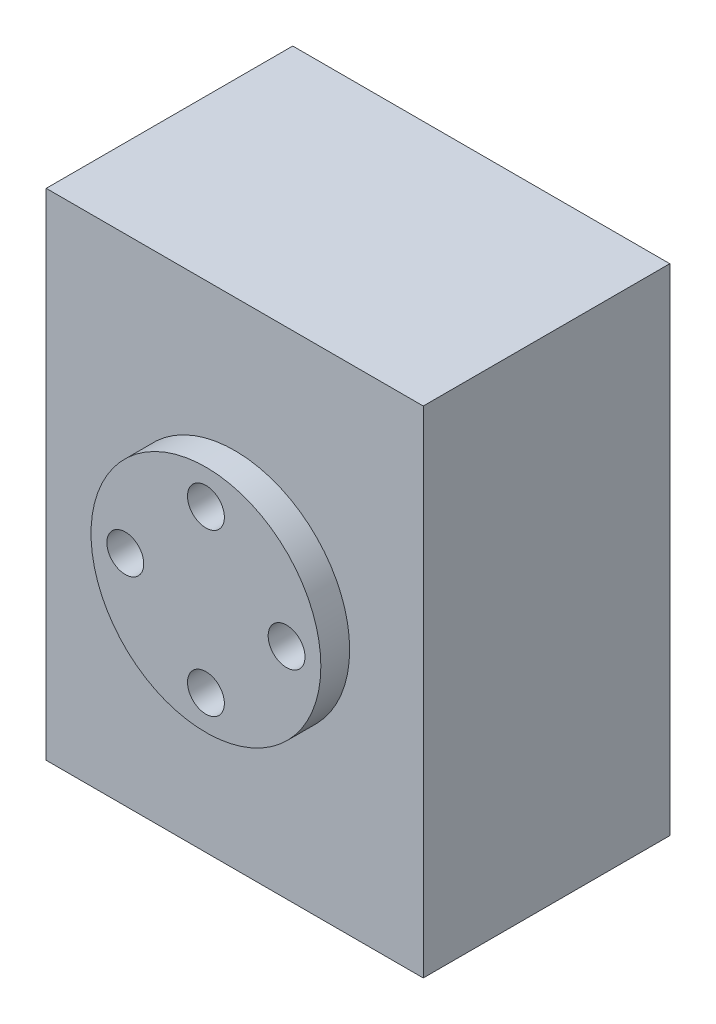
SolidWorks part; units mm, degrees
ref_plane "Front Plane" through (0, 0, 0) normal (0, 0, 1) x (1, 0, 0)
ref_plane "Top Plane" through (0, 0, 0) normal (0, 1, 0) x (1, 0, 0)
ref_plane "Right Plane" through (0, 0, 0) normal (1, 0, 0) x (0, 0, -1)
sketch "Sketch1" plane through (0, 0, 0) normal (0, 0, 1) x (1, 0, 0)
  circle A0 centre (0, 0) radius 9.975
  dimension "D1" = 19.95
extrude "Boss-Extrude1" add sketch "Sketch1" along normal blind 2.5
sketch "Sketch3" plane through (0, 0, 0) normal (0, 0, -1) x (-1, 0, 0)
  line L0 (16.365, 21.5) -> (16.365, -21.5)
  line L1 (-12.365, 17.5) -> (12.365, 17.5)
  line L2 (-12.365, 17.5) -> (-12.365, -17.5)
  line L3 (-12.365, -17.5) -> (12.365, -17.5)
  line L4 (12.365, 17.5) -> (12.365, -17.5)
  line L5 (-12.365, 17.5) -> (12.365, -17.5) construction
  line L6 (-12.365, -17.5) -> (12.365, 17.5) construction
  line L7 (-16.365, -21.5) -> (16.365, -21.5)
  line L8 (-16.365, 21.5) -> (-16.365, -21.5)
  line L9 (-16.365, 21.5) -> (16.365, 21.5)
  point P0 (0, 0)
  dimension "D1" = 35
  dimension "D2" = 24.73
  dimension "D3" = 4
extrude "Boss-Extrude4" add sketch "Sketch3" along normal blind 2.5 contours L2 L1 L4 L3
extrude "Boss-Extrude5" add sketch "Sketch3<5>" along normal blind 21.4
sketch "Sketch3<5>" plane through (0, 0, 0) normal (0, 0, -1) x (-1, 0, 0) same geometry as "Sketch3"
sketch "Sketch4" plane through (0, 0, -2.5) normal (0, 0, -1) x (-1, 0, 0)
  line L1 (12.365, 17.5) -> (7.165, 17.5)
  line L2 (12.365, 17.5) -> (12.365, 16.4)
  line L3 (12.365, 16.4) -> (7.165, 16.4)
  line L4 (7.165, 17.5) -> (7.165, 16.4)
  line L5 (-12.365, 17.5) -> (-7.165, 17.5)
  line L6 (-12.365, 17.5) -> (-12.365, 16.4)
  line L7 (-12.365, 16.4) -> (-7.165, 16.4)
  line L8 (-7.165, 17.5) -> (-7.165, 16.4)
  line L9 (12.365, -17.5) -> (9.165, -17.5)
  line L10 (12.365, -17.5) -> (12.365, -16)
  line L11 (12.365, -16) -> (9.165, -16)
  line L12 (9.165, -17.5) -> (9.165, -16)
  line L13 (-12.365, -17.5) -> (-9.165, -17.5)
  line L14 (-12.365, -17.5) -> (-12.365, -16)
  line L15 (-12.365, -16) -> (-9.165, -16)
  line L16 (-9.165, -17.5) -> (-9.165, -16)
  dimension "D1" = 1.1
  dimension "D2" = 5.2
  dimension "D3" = 5.2
  dimension "D4" = 1.1
  dimension "D5" = 3.2
  dimension "D6" = 1.5
  dimension "D7" = 3.2
extrude "Boss-Extrude6" add sketch "Sketch4" along normal blind 18.9 contours L2 L1 L4 L3 | L6 L5 L8 L7 | L10 L9 L12 L11 | L14 L13 L16 L15
sketch "Sketch6" plane through (0, 0, -2.5) normal (0, 0, -1) x (-1, 0, 0)
  line L1 (9.165, -17.5) -> (-9.165, -17.5)
  line L2 (9.165, -17.5) -> (9.165, -16)
  line L3 (9.165, -16) -> (-9.165, -16)
  line L4 (-9.165, -17.5) -> (-9.165, -16)
extrude "Boss-Extrude7" add sketch "Sketch6" along normal blind 5.3
sketch "Sketch2" plane through (0, 0, 2.5) normal (0, 0, 1) x (1, 0, 0)
  circle A0 centre (0, 0) radius 7 construction
  circle A1 centre (7, 0) radius 1.6
  circle A2 centre (0, -7) radius 1.6
  circle A3 centre (-7, 0) radius 1.6
  circle A4 centre (0, 7) radius 1.6
  point P14 (0, 0)
  dimension "D1" = 14
  dimension "D2" = 3.2
  dimension "D3" = 4
extrude "Cut-Extrude1" cut sketch "Sketch2" against normal blind 37
